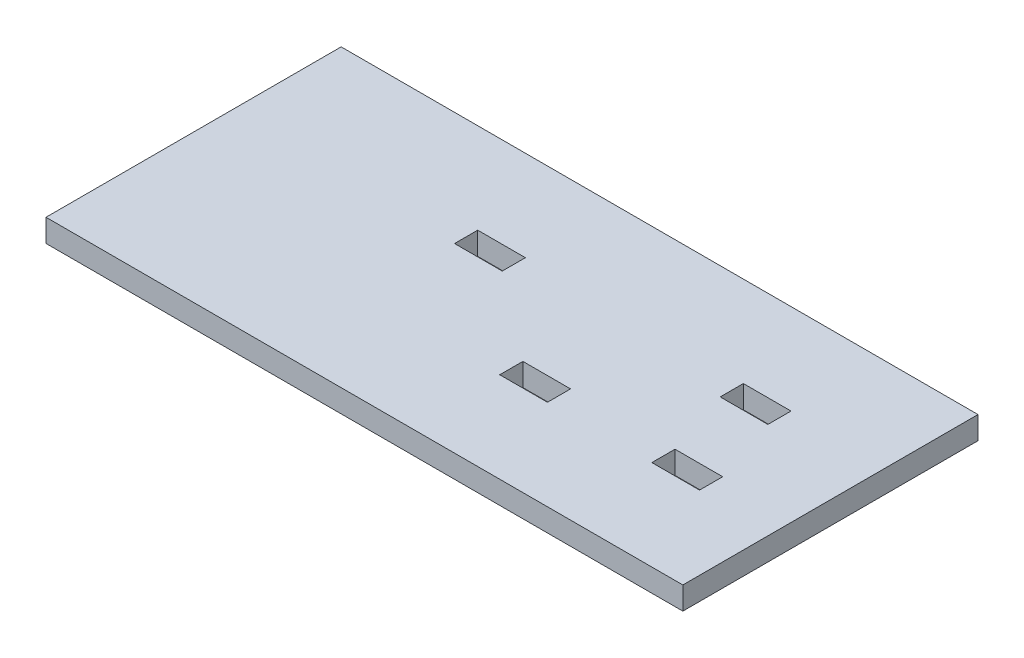
SolidWorks part; units mm, degrees
ref_plane "Front Plane" through (0, 0, 0) normal (0, 0, 1) x (1, 0, 0)
ref_plane "Top Plane" through (0, 0, 0) normal (0, 1, 0) x (1, 0, 0)
ref_plane "Right Plane" through (0, 0, 0) normal (1, 0, 0) x (0, 0, -1)
sketch "Sketch1" plane through (0, 0, 0) normal (0, 1, 0) x (1, 0, 0)
  line L0 (48.875, 7.475) -> (53.875, -7.475) construction
  line L1 (-70.125, -32.5) -> (70.125, -32.5)
  line L2 (-70.125, -32.5) -> (-70.125, 32.5)
  line L3 (-70.125, 32.5) -> (70.125, 32.5)
  line L4 (70.125, -32.5) -> (70.125, 32.5)
  line L5 (-70.125, -32.5) -> (70.125, 32.5) construction
  line L6 (-70.125, 32.5) -> (70.125, -32.5) construction
  line L7 (-20.125, 7.475) -> (-9.625, 7.475)
  line L8 (-20.125, 7.475) -> (-20.125, 12.575)
  line L9 (-20.125, 12.575) -> (-9.625, 12.575)
  line L10 (-9.625, 7.475) -> (-9.625, 12.575)
  line L11 (38.375, 7.475) -> (48.875, 7.475)
  line L12 (38.375, 7.475) -> (38.375, 12.575)
  line L13 (38.375, 12.575) -> (48.875, 12.575)
  line L14 (48.875, 7.475) -> (48.875, 12.575)
  line L15 (9.875, -12.575) -> (20.375, -12.575)
  line L16 (9.875, -12.575) -> (9.875, -7.475)
  line L17 (9.875, -7.475) -> (20.375, -7.475)
  line L18 (20.375, -12.575) -> (20.375, -7.475)
  line L19 (43.375, -12.575) -> (53.875, -12.575)
  line L20 (43.375, -12.575) -> (43.375, -7.475)
  line L21 (43.375, -7.475) -> (53.875, -7.475)
  line L22 (53.875, -12.575) -> (53.875, -7.475)
  point P0 (0, 0)
  point P22 (51.375, 0)
  point P23 (55.6698, -7.475)
  point P26 (43.625, 12.575)
  point P27 (15.125, -7.475)
  point P28 (-14.875, 12.575)
  dimension "D1" = 5.1
  dimension "D2" = 14.95
  dimension "D3" = 25.15
  dimension "D4" = 10.5
  dimension "D5" = 26.5
  dimension "D6" = 55
  dimension "D7" = 85
  dimension "D8" = 50
  dimension "D9" = 65
  dimension "D10" = 5
base flange "Base-Flange1" sketch "Sketch1" thickness 5 reverse thickness direction no parameters "D1"=0.7366
sketch "Bend-Lines1" [suppressed] plane through (0, 0, 0) normal (0, 1, 0) x (1, 0, 0)
sketch "Bounding-Box1" [suppressed] plane through (0, 0, 0) normal (0, 1, 0) x (1, 0, 0)
sheet metal parameters "Sheet-Metal1" thickness 5 parameters "D1"=0.7366
flat pattern "Flat-Pattern1" [suppressed]
sketch "Bend-Lines2"
sketch3d "Bounding-Box2" [suppressed]
  line L0 (-65.125, 32.5, 0) -> (65.125, 32.5, 0) construction
  line L1 (-65.125, -32.5, 0) -> (65.125, -32.5, 0) construction
  line L2 (-65.125, 32.5, 0) -> (-65.125, -32.5, 0) construction
  line L3 (65.125, 32.5, 0) -> (65.125, -32.5, 0) construction
